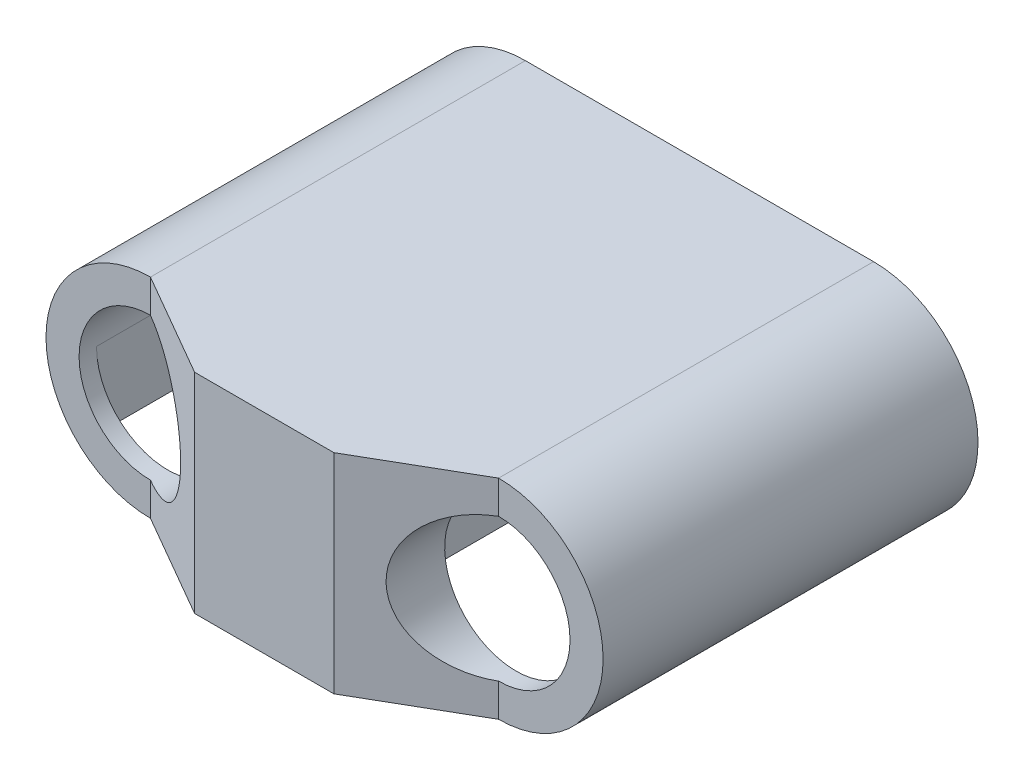
SolidWorks part; units mm, degrees
ref_plane "Front Plane" through (0, 0, 0) normal (0, 0, 1) x (1, 0, 0)
ref_plane "Top Plane" through (0, 0, 0) normal (0, 1, 0) x (1, 0, 0)
ref_plane "Right Plane" through (0, 0, 0) normal (1, 0, 0) x (0, 0, -1)
sketch "Sketch1" plane through (0, 0, 0) normal (0, 0, 1) x (1, 0, 0)
  line L0 (-100, 0) -> (100, 0) construction
  line L1 (0, 0) -> (0, 50) construction
  line L2 (-100, 0) -> (100, 0) construction
  line L3 (-100, 60) -> (100, 60)
  line L4 (-100, -60) -> (100, -60)
  circle A0 centre (100, 0) radius 41
  circle A1 centre (-100, 0) radius 41
  circle A2 centre (100, 0) radius 49 construction
  circle A3 centre (-100, 0) radius 49 construction
  arc A4 (-100, 60) -> (-100, -60) centre (-100, 0) ccw
  arc A5 (100, -60) -> (100, 60) centre (100, 0) ccw
  point P9 (0, 0)
  dimension "D1" = 82
  dimension "D4" = 98
  dimension "D5" = 60
  dimension "D2" = 100
  dimension "D3" = 50
extrude "Boss-Extrude1" add sketch "Sketch1" along normal blind 250
sketch "Sketch4" plane through (0, 0, 0) normal (0, 0, 1) x (1, 0, 0)
  line L1 (-100, -55) -> (100, -55)
  line L6 (-100, 55) -> (-100, 75)
  line L7 (-100, 75) -> (100, 75)
  line L8 (100, 75) -> (100, 55)
  arc A0 (-100, 55) -> (-100, -55) centre (-100, 0) ccw
  arc A1 (100, -55) -> (100, 55) centre (100, 0) ccw
  dimension "D1" = 55
  dimension "D4" = 55
  dimension "D2" = 100
  dimension "D3" = 100
  dimension "D5" = 200
  dimension "D6" = 100
  dimension "D7" = 100
  dimension "D8" = 20
  dimension "D9" = 200
sketch "Sketch5" plane through (0, 0, 0) normal (0, 1, 0) x (1, 0, 0)
  line L1 (100, -250) -> (-100, -250) construction
  line L3 (40, -250) -> (-40, -250)
  line L4 (-40, -250) -> (-100, -215.359)
  line L5 (-100, -250) -> (-100, 0) construction
  line L6 (-100, -215.359) -> (-160, -215.359)
  line L7 (-160, -215.359) -> (-160, -312.3312)
  line L8 (-160, -312.3312) -> (8.3267, -312.3312)
  line L9 (-160, 0) -> (-160, -250) construction
  line L12 (160, -312.3312) -> (-8.3267, -312.3312)
  line L13 (160, -215.359) -> (160, -312.3312)
  line L14 (100, -215.359) -> (160, -215.359)
  line L15 (40, -250) -> (100, -215.359)
  dimension "D2" = 30
extrude "Cut-Extrude2" cut sketch "Sketch5" against normal mid plane 260 contours L15 L3 L4 L6 L7 L8 L12 L13 L14 region at (0, 0, 270.0764)
sketch "Sketch6" plane through (0, 0, 0) normal (0, 1, 0) x (1, 0, 0)
  line L0 (0, -250) -> (0, 0) construction
  line L1 (40, -250) -> (-40, -250) construction
  line L2 (100, 0) -> (-100, 0) construction
  line L3 (160, -173.3468) -> (36.3203, -173.3468)
  line L4 (160, -215.359) -> (160, 0) construction
  line L5 (36.3203, -173.3468) -> (25.094, -162.1206)
sketch "Sketch7" plane through (0, 0, 0) normal (0, 0, -1) x (-1, 0, 0)
  line L0 (-100, 41) -> (-5, 41) construction
  line L1 (0, 41) -> (0, 0) construction
  line L2 (100, 41) -> (5, 41)
  line L3 (141, 0) -> (141, -85.7279)
  line L4 (-141, 0) -> (-141, -85.7279)
  line L5 (-141, -85.7279) -> (-5, -85.7279)
  line L6 (-5, 41) -> (-5, -85.7279)
  line L7 (5, 41) -> (5, -85.7279)
  line L8 (5, 41) -> (100, 41) construction
  line L9 (-5, 41) -> (-100, 41)
  line L10 (5, -85.7279) -> (141, -85.7279)
  circle A0 centre (-100, 0) radius 41 construction
  arc A1 (-100, 41) -> (-141, 0) centre (-100, 0) ccw
  arc A2 (100, 41) -> (141, 0) centre (100, 0) cw
  point P14 (0, -85.7279)
  dimension "D1" = 5
extrude "Cut-Extrude3" cut sketch "Sketch7" against normal offset from surface (205.359 mm away) 10 up to face at (125.25, 0, 215.359)
fillet "Fillet1" radius 5 4 edges at (5, -9.5, 205.359) (5, 41, 102.6795) (-5, 41, 102.6795) (-5, -9.5, 205.359)
